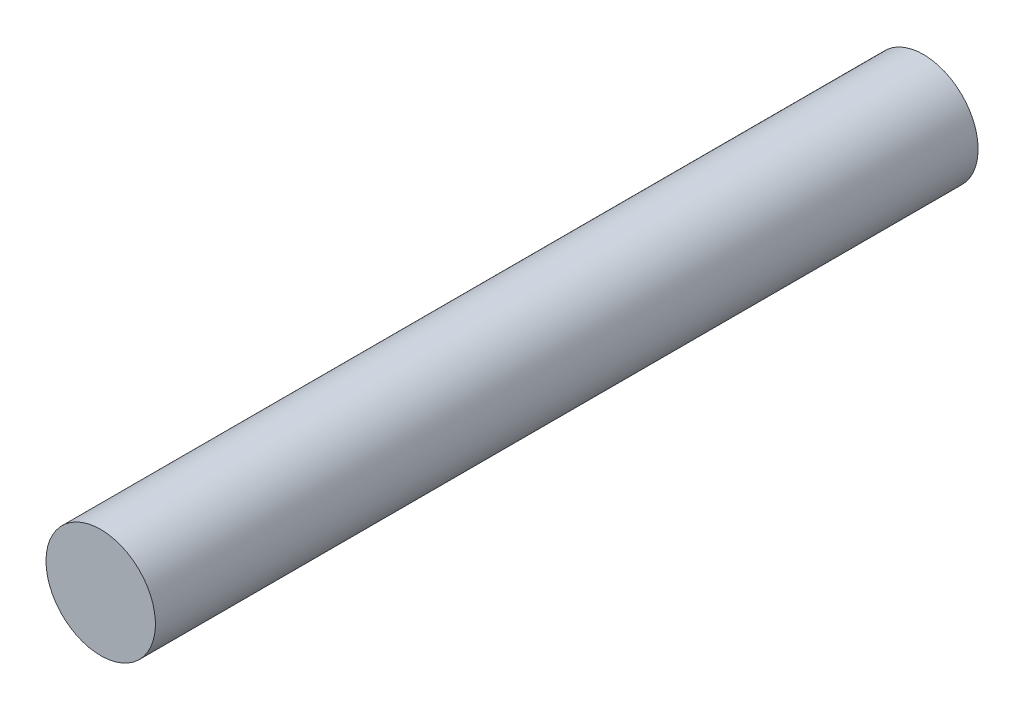
SolidWorks part; units mm, degrees
material "Hexcel AS4C (3000 Filaments)"
ref_plane "Front" through (0, 0, 0) normal (0, 0, 1) x (1, 0, 0)
ref_plane "Top" through (0, 0, 0) normal (0, 1, 0) x (1, 0, 0)
ref_plane "Right" through (0, 0, 0) normal (1, 0, 0) x (0, 0, -1)
sketch "Sketch1" plane through (0, 0, 0) normal (0, 0, 1) x (1, 0, 0)
  circle A0 centre (0, 0) radius 3.175
  dimension "D1" = 6.35
extrude "Boss-Extrude1" add sketch "Sketch1" along normal blind 47.752
equation "\"truss_member_od\" = .25in"
equation "\"truss_member_L1\" = 2.125in"
equation "\"connector_hole_depth\" = .375in"
equation "\"truss_member_L2\" = 3in"
equation "\"D1@Boss-Extrude1\"=\"truss_member_L1\""
equation "\"D1@Sketch1\"=\"truss_member_od\""
